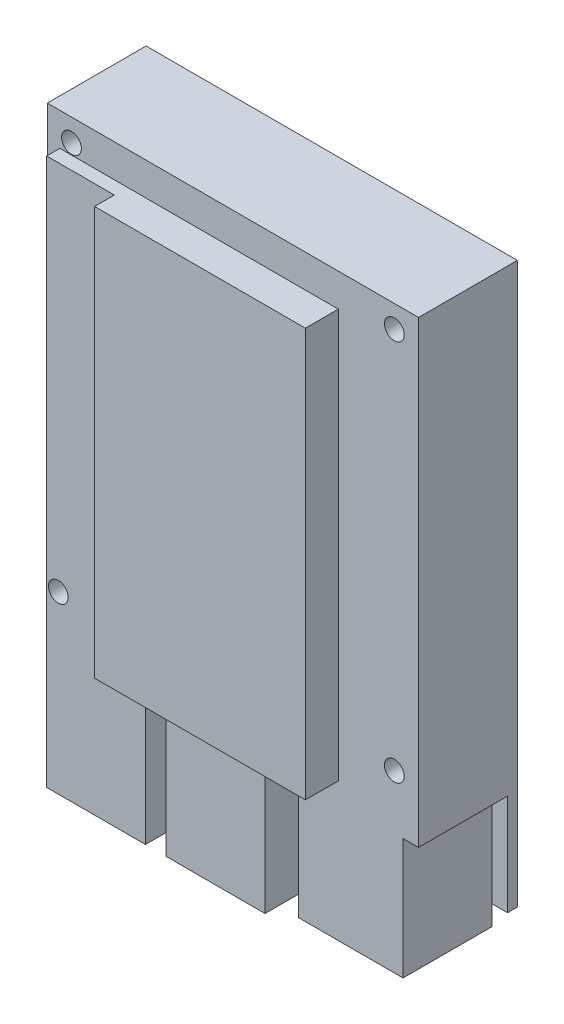
SolidWorks part; units mm, degrees
ref_plane "Front Plane" through (0, 0, 0) normal (0, 0, 1) x (1, 0, 0)
ref_plane "Top Plane" through (0, 0, 0) normal (0, 1, 0) x (1, 0, 0)
ref_plane "Right Plane" through (0, 0, 0) normal (1, 0, 0) x (0, 0, -1)
sketch "Sketch1" plane through (0, 0, 0) normal (0, 0, 1) x (1, 0, 0)
  line L1 (0, 0) -> (56.35, 0)
  line L2 (0, 0) -> (0, 85)
  line L3 (0, 85) -> (56.35, 85)
  line L4 (56.35, 0) -> (56.35, 85)
  dimension "D1" = 56.35
  dimension "D2" = 85
extrude "Boss-Extrude1" add sketch "Sketch1" along normal blind 55.5
sketch "Sketch2" plane through (0, 0, 0) normal (0, -1, 0) x (1, 0, 0)
  line L0 (0, 0) -> (56.35, 0) construction
  line L1 (1.9, 52.5) -> (16.9, 52.5)
  line L2 (1.9, 52.5) -> (1.9, 37)
  line L3 (1.9, 37) -> (16.9, 37)
  line L4 (16.9, 52.5) -> (16.9, 37)
  line L5 (20.05, 52.5) -> (35.05, 52.5)
  line L6 (20.05, 52.5) -> (20.05, 37)
  line L7 (20.05, 37) -> (35.05, 37)
  line L8 (35.05, 52.5) -> (35.05, 37)
  line L9 (38.1, 50.5) -> (54, 50.5)
  line L10 (38.1, 50.5) -> (38.1, 37)
  line L11 (38.1, 37) -> (54, 37)
  line L12 (54, 50.5) -> (54, 37)
  line L13 (56.35, 55.5) -> (56.35, 0) construction
  line L14 (0, 55.5) -> (0, 0) construction
  line L15 (0, 37) -> (56.35, 37)
  line L16 (0, 37) -> (0, 35.6)
  line L17 (0, 35.6) -> (56.35, 35.6)
  line L18 (56.35, 37) -> (56.35, 35.6)
  line L19 (0, 55.5) -> (56.35, 55.5) construction
  line L20 (0, 26.7) -> (56.35, 26.7)
  line L21 (0, 26.7) -> (0, 25.1)
  line L22 (0, 25.1) -> (56.35, 25.1)
  line L23 (56.35, 26.7) -> (56.35, 25.1)
  line L24 (5.575, 25.1) -> (50.775, 25.1)
  line L25 (5.575, 25.1) -> (5.575, 6)
  line L26 (11.575, 0) -> (44.775, 0)
  line L27 (50.775, 25.1) -> (50.775, 6)
  line L29 (12.175, 55.5) -> (44.175, 55.5)
  line L30 (12.175, 55.5) -> (12.175, 37)
  line L31 (12.175, 37) -> (44.175, 37)
  line L32 (44.175, 55.5) -> (44.175, 37)
  arc A0 (44.775, 0) -> (50.775, 6) centre (44.775, 6) ccw
  arc A1 (5.575, 6) -> (11.575, 0) centre (11.575, 6) ccw
  point P32 (28.175, 55.5)
  point P33 (28.175, 0)
  point P36 (50.775, 0)
  point P43 (28.175, 37)
  line M8 (0, 0) -> (56.35, 0)
  line M9 (56.35, 0) -> (56.35, 55.5)
  line M10 (56.35, 55.5) -> (0, 55.5)
  line M11 (0, 55.5) -> (0, 0)
  dimension "D15" = 6
  dimension "D1" = 15
  dimension "D2" = 15
  dimension "D3" = 15.9
  dimension "D4" = 13.5
  dimension "D5" = 15.5
  dimension "D6" = 15.5
  dimension "D7" = 37
  dimension "D8" = 52.1
  dimension "D9" = 3.15
  dimension "D10" = 2.35
  dimension "D11" = 1.4
  dimension "D12" = 1.6
  dimension "D13" = 8.9
  dimension "D14" = 45.2
  dimension "D16" = 32
extrude "Cut-Extrude3" cut sketch "Sketch2" against normal through all contours A1 L25 L22 M11 M8 | A0 L22 L27 M8 M9 | L32 L9 L12 L15 M10 M9 | L30 L15 L2 L1 M10 M11 region at (1.6785, 0, 44.75) region at (50.2625, 0, 55.2785) region at (3.0035, 0, 11.9635) region at (53.3465, 0, 11.9635)
extrude "Cut-Extrude4" cut sketch "Sketch2<3>" against normal blind 18 contours L32 L30 L1 L4 L15 L6 L5 L8 L10 L9 M10 region at (12.5446, 0, 54)
sketch "Sketch2<3>" plane through (0, 0, 0) normal (0, -1, 0) x (1, 0, 0) same geometry as "Sketch2"
extrude "Boss-Extrude2" add sketch "Sketch2<4>" along normal blind 3 contours L30 L1 L2 L3 | L1 L30 L15 L4 | L8 L5 L6 L7 | L32 L9 L10 L11 | L9 L32 L15 L12 region at (7.0375, 0, 44.75) region at (14.5375, 0, 44.75) region at (27.55, 0, 44.75) region at (41.1375, 0, 43.75) region at (49.0875, 0, 43.75)
sketch "Sketch2<4>" plane through (0, 0, 0) normal (0, -1, 0) x (1, 0, 0) same geometry as "Sketch2"
sketch "Sketch3" plane through (1.9, 0, 0) normal (-1, 0, 0) x (0, 0, 1)
  line L0 (37, 85) -> (37, 0) construction
  line L1 (37, 79.7) -> (43.5, 79.7)
  line L2 (37, 79.7) -> (37, 27.2)
  line L3 (37, 27.2) -> (43.5, 27.2)
  line L4 (43.5, 79.7) -> (43.5, 27.2)
  line L5 (25.1, 85) -> (25.1, 0) construction
  line L6 (26.5, 79.7) -> (33, 79.7)
  line L7 (26.5, 79.7) -> (26.5, 27.2)
  line L8 (26.5, 27.2) -> (33, 27.2)
  line L9 (33, 79.7) -> (33, 27.2)
  line L10 (37, 85) -> (25.1, 85) construction
  dimension "D1" = 1.4
  dimension "D2" = 6.5
  dimension "D3" = 6.5
  dimension "D4" = 52.5
  dimension "D5" = 5.3
extrude "Boss-Extrude3" add sketch "Sketch3" along normal blind 2.4
sketch "Sketch4" plane through (0, 0, 0) normal (0, -1, 0) x (1, 0, 0)
  line L0 (38.1, 50.5) -> (54, 50.5) construction
  line L1 (-13.2262, -5.8848) -> (70.0104, -5.8848)
  line L2 (-13.2262, -5.8848) -> (-13.2262, 35.5)
  line L3 (-13.2262, 35.5) -> (70.0104, 35.5)
  line L4 (70.0104, -5.8848) -> (70.0104, 35.5)
  dimension "D1" = 15
extrude "Cut-Extrude5" cut sketch "Sketch4" against normal through all
sketch "Sketch6" plane through (0, 0, 50.5) normal (0, 0, 1) x (1, 0, 0)
  line L0 (56.35, 85) -> (56.35, 0) construction
  line L1 (0, 85) -> (56.35, 85)
  line L2 (0, 85) -> (0, 15.3341)
  line L3 (0, 15.3341) -> (56.35, 15.3341)
  line L4 (56.35, 85) -> (56.35, 15.3341)
extrude "Boss-Extrude4" add sketch "Sketch6" against normal up to surface (13.5 mm away) up to face at (0.95, 13.6, 37)
sketch "Sketch5" plane through (0, 0, 35.5) normal (0, 0, -1) x (-1, 0, 0)
  line L0 (-38.1, -3) -> (-54, -3) construction
  line L1 (-52.675, 81.6) -> (-3.675, 81.6) construction
  line L2 (-52.675, 81.6) -> (-52.675, 23.6) construction
  line L3 (-52.675, 23.6) -> (-3.675, 23.6) construction
  line L4 (-3.675, 81.6) -> (-3.675, 23.6) construction
  line L6 (-56.35, 85) -> (0, 85) construction
  circle A0 centre (-52.675, 81.6) radius 1.5
  circle A1 centre (-3.675, 81.6) radius 1.5
  circle A2 centre (-3.675, 23.6) radius 1.5
  circle A3 centre (-52.675, 23.6) radius 1.5
  point P13 (-28.175, 85)
  point P14 (-28.175, 81.6)
  dimension "D4" = 3
  dimension "D1" = 58
  dimension "D2" = 49
  dimension "D3" = 26.6
extrude "Cut-Extrude6" cut sketch "Sketch5" against normal through all
sketch "Sketch7" plane through (0, 0, 55.5) normal (0, 0, 1) x (1, 0, 0)
  line L0 (1.9, 85) -> (12.175, 85) construction
  line L1 (-13.2086, 116.0458) -> (88.375, 116.0458)
  line L2 (-13.2086, 116.0458) -> (-13.2086, 80)
  line L3 (-13.2086, 80) -> (88.375, 80)
  line L4 (88.375, 116.0458) -> (88.375, 80)
  dimension "D1" = 5
extrude "Cut-Extrude7" cut sketch "Sketch7" against normal blind 5
